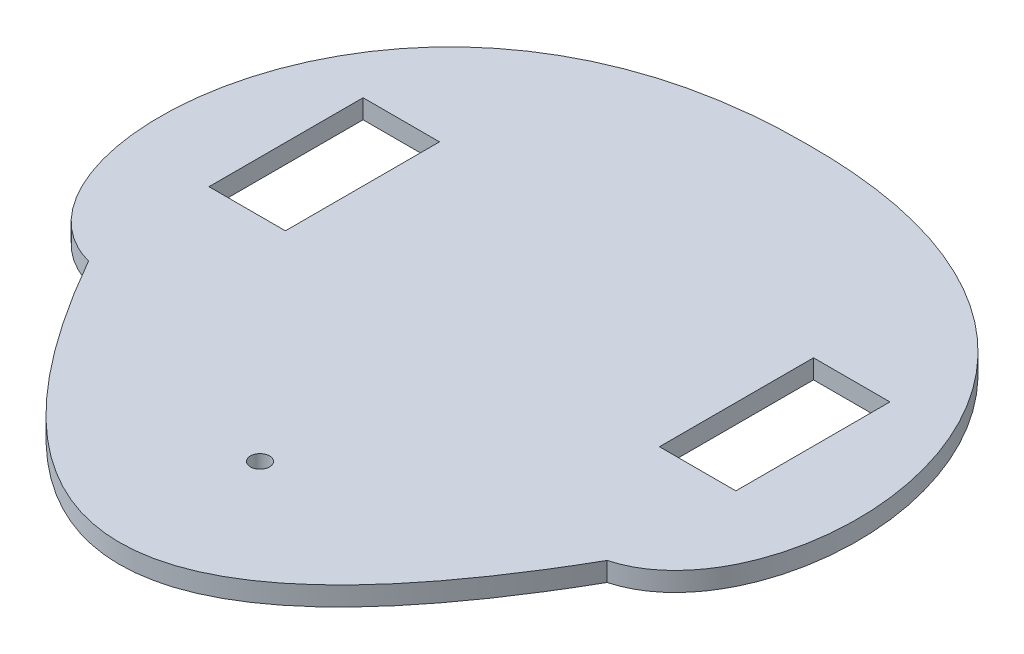
SolidWorks part; units mm, degrees
ref_plane "Front Plane" through (0, 0, 0) normal (0, 0, 1) x (1, 0, 0)
ref_plane "Top Plane" through (0, 0, 0) normal (0, 1, 0) x (1, 0, 0)
ref_plane "Right Plane" through (0, 0, 0) normal (1, 0, 0) x (0, 0, -1)
sketch "Sketch1" plane through (0, 0, 0) normal (0, 1, 0) x (1, 0, 0)
  line L0 (-76.4376, 0) -> (59.0806, 0) construction
  line L1 (59.0806, -59.6545) -> (-76.4376, -59.6545) construction
  line L2 (-76.4376, 0) -> (-76.4376, -59.6545) construction
  line L3 (59.0806, 0) -> (59.0806, -59.6545) construction
  line L4 (-8.6785, -59.6545) -> (-8.6785, 120.3455) construction
  line L5 (-115.0944, 120.3455) -> (89.7208, 120.3455) construction
  line L6 (-8.6785, 52.7015) -> (-67.5408, 52.7015) construction
  line L7 (-11.131, 90.3529) -> (-11.131, 0) construction
  line L8 (-67.5408, 120.3455) -> (-67.5408, 52.7015) construction
  line L9 (-41.6908, 0) -> (-41.6908, -59.6545) construction
  line L10 (60.1705, 32.5659) -> (40.1969, 32.5659)
  line L11 (-77.5276, 72.8372) -> (-57.554, 72.8372)
  line L12 (-77.5276, 72.8372) -> (-77.5276, 32.5659)
  line L13 (-77.5276, 32.5659) -> (-57.554, 32.5659)
  line L14 (-57.554, 72.8372) -> (-57.554, 32.5659)
  line L15 (-77.5276, 72.8372) -> (-57.554, 32.5659) construction
  line L16 (-77.5276, 32.5659) -> (-57.554, 72.8372) construction
  line L17 (40.1969, 72.8372) -> (40.1969, 32.5659)
  line L18 (60.1705, 72.8372) -> (40.1969, 72.8372)
  line L19 (60.1705, 72.8372) -> (60.1705, 32.5659)
  line L20 (60.1705, 32.5659) -> (40.1969, 72.8372) construction
  line L21 (-76.4376, -22.9437) -> (59.0806, -22.9437) construction
  line L22 (60.1705, 72.8372) -> (40.1969, 32.5659) construction
  circle A0 centre (-8.6785, -22.9437) radius 2.5
  spline S0 degree 2 poles (-76.4376, 0) (-8.6785, -119.309) (59.0806, 0) knots 0 0 0 1 1 1
  spline S1 degree 3 poles (-76.4376, 0) (-115.8317, 10.5546) (-112.8828, 121.0713) (-8.6785, 120.3455) knots 0 0 0 0 1 1 1 1
  spline S2 degree 3 poles (59.0806, 0) (98.4746, 10.5546) (95.5258, 121.0713) (-8.6785, 120.3455) knots 0 0 0 0 1 1 1 1
  point P26 (50.1837, 52.7015)
  dimension "D1" = 180
  dimension "D2" = 5
extrude "Boss-Extrude1" add sketch "Sketch1" along normal blind 5
